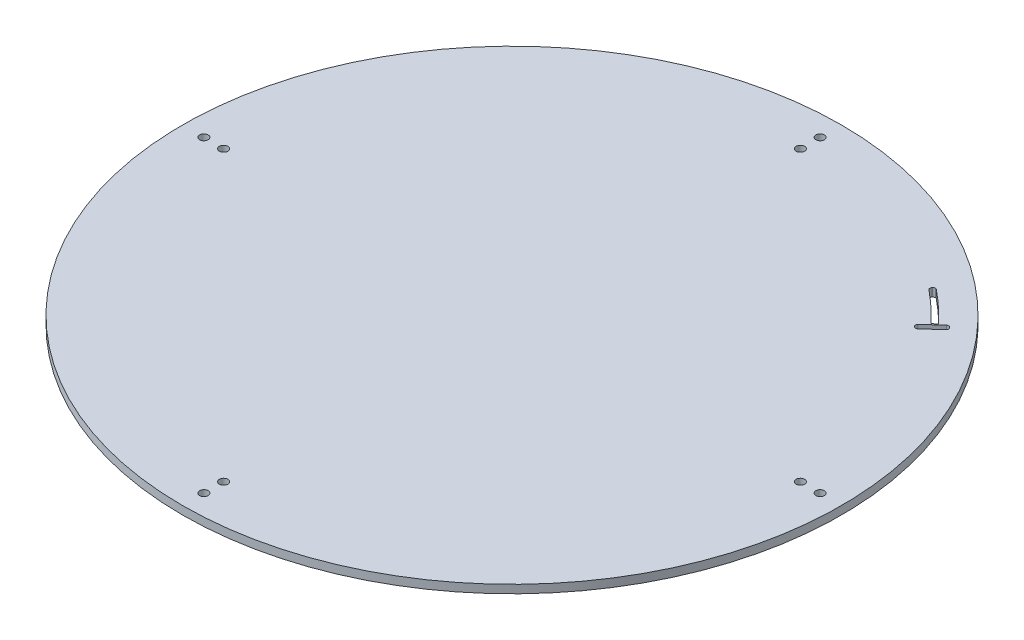
SolidWorks part; units mm, degrees
ref_plane "前视基准面" through (0, 0, 0) normal (0, 0, 1) x (1, 0, 0)
ref_plane "上视基准面" through (0, 0, 0) normal (0, 1, 0) x (1, 0, 0)
ref_plane "右视基准面" through (0, 0, 0) normal (1, 0, 0) x (0, 0, -1)
ref_axis "中心轴" through (0, -55, 0) along (0, 1, 0)
sketch "草图1" plane through (0, 0, 0) normal (0, 1, 0) x (1, 0, 0)
  circle A0 centre (0, 0) radius 200
extrude "主体" add sketch "草图1" along normal blind 5
sketch "草图2" plane through (0, 5, 0) normal (0, 1, 0) x (1, 0, 0)
  line L0 (0, 0) -> (0, 120.98) construction
  circle A0 centre (0, 0) radius 200
  circle A1 centre (0, 0) radius 187 construction
  circle A2 centre (0, 0) radius 200 construction
  circle A3 centre (0, 0) radius 175 construction
  circle A6 centre (0, -175) radius 2.6
  circle A7 centre (0, -187) radius 2.6
extrude "切除-拉伸3" cut sketch "草图2" against normal up to next contours A6 | A7 region at (0, 5, 175) region at (0, 5, 187)
pattern_circular "阵列(圆周)1" count 4 over 360 about axis through (0, -55, 0) along (0, 1, 0) of "切除-拉伸3"
sketch "草图4" plane through (0, 0, 0) normal (0.682, 0, 0.7314) x (0.7314, 0, -0.682)
  line L0 (180, -3) -> (187.114, -3) construction
  line L1 (180, 9) -> (183, 9) construction
  line L2 (180, 9) -> (180, -3) construction
  line L3 (180, -3) -> (183, -3) construction
  line L4 (183, 9) -> (183, -3) construction
  line L5 (183.1, 9.1) -> (183.1, -3.1)
  line L6 (179.9, -3.1) -> (183.1, -3.1)
  line L7 (179.9, 9.1) -> (179.9, -3.1)
  line L8 (179.9, 9.1) -> (183.1, 9.1)
  line L11 (180, 10.5) -> (180, -3) construction
  line L12 (183, 10.5) -> (183, 0) construction
  dimension "D1" = 0.1
revolve "切除-旋转3" cut sketch "草图4" angle 8.5 about axis through (0, -55, 0) along (0, 1, 0)
fillet "圆角2" radius 1.5 2 edges at (111.9904, 2.5, -140.7912) (113.9824, 2.5, -143.2956)
sketch "草图6" plane through (0, 5, 0) normal (0, 1, 0) x (1, 0, 0)
  line L0 (127.0908, 117.3682) -> (138.046, 127.4853) construction
  line L4 (140.2499, 125.0567) -> (129.1198, 115.1323) construction
  line L5 (130.9845, 116.795) -> (139.9413, 124.7815) construction
  line L7 (128.9262, 119.0632) -> (137.7423, 127.2048) construction
  line L8 (126.9494, 117.3738) -> (138.0516, 127.6266)
  line L9 (140.391, 125.0485) -> (129.1116, 114.991)
  arc A0 (140.2499, 125.0567) -> (138.046, 127.4853) centre (0, 0) ccw construction
  arc A1 (129.1198, 115.1323) -> (127.0908, 117.3682) centre (0, 0) ccw construction
  arc A4 (140.391, 125.0485) -> (138.0516, 127.6266) centre (0, 0) ccw
  arc A5 (129.1116, 114.991) -> (126.9494, 117.3738) centre (0, 0) ccw
  dimension "D1" = 0.1
extrude "开孔" cut sketch "草图6" against normal up to next
fillet "圆角1" radius 1.5 4 edges at (129.1116, 2.5, -114.991) (140.391, 2.5, -125.0485) (138.0516, 2.5, -127.6266) (126.9494, 2.5, -117.3738)
